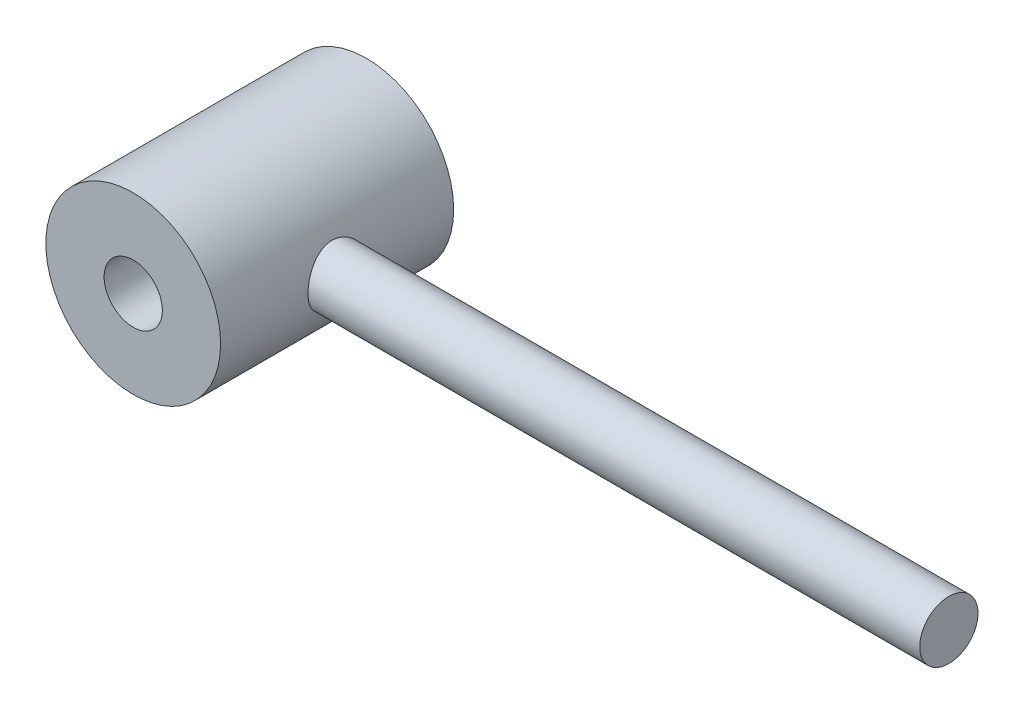
SolidWorks part; units mm, degrees
ref_plane "Front" through (0, 0, 0) normal (0, 0, 1) x (1, 0, 0)
ref_plane "Top" through (0, 0, 0) normal (0, 1, 0) x (1, 0, 0)
ref_plane "Right" through (0, 0, 0) normal (1, 0, 0) x (0, 0, -1)
sketch "Sketch1" plane through (0, 0, 0) normal (1, 0, 0) x (0, 0, -1)
  circle A0 centre (0, 0) radius 6.35
  dimension "D1" = 12.7
extrude "Boss-Extrude1" add sketch "Sketch1" along normal blind 152.4
sketch "Sketch2" plane through (0, 0, 0) normal (0, 0, 1) x (1, 0, 0)
  circle A0 centre (0, 0) radius 19.05
  dimension "D1" = 38.1
extrude "Boss-Extrude2" add sketch "Sketch2" along normal blind 25.4 and the other way blind 25.4
sketch "Sketch3" plane through (0, 0, 25.4) normal (0, 0, 1) x (1, 0, 0)
  circle A1 centre (0, 0) radius 6.35
  dimension "D1" = 12.7
extrude "Cut-Extrude1" cut sketch "Sketch3" against normal up to next
